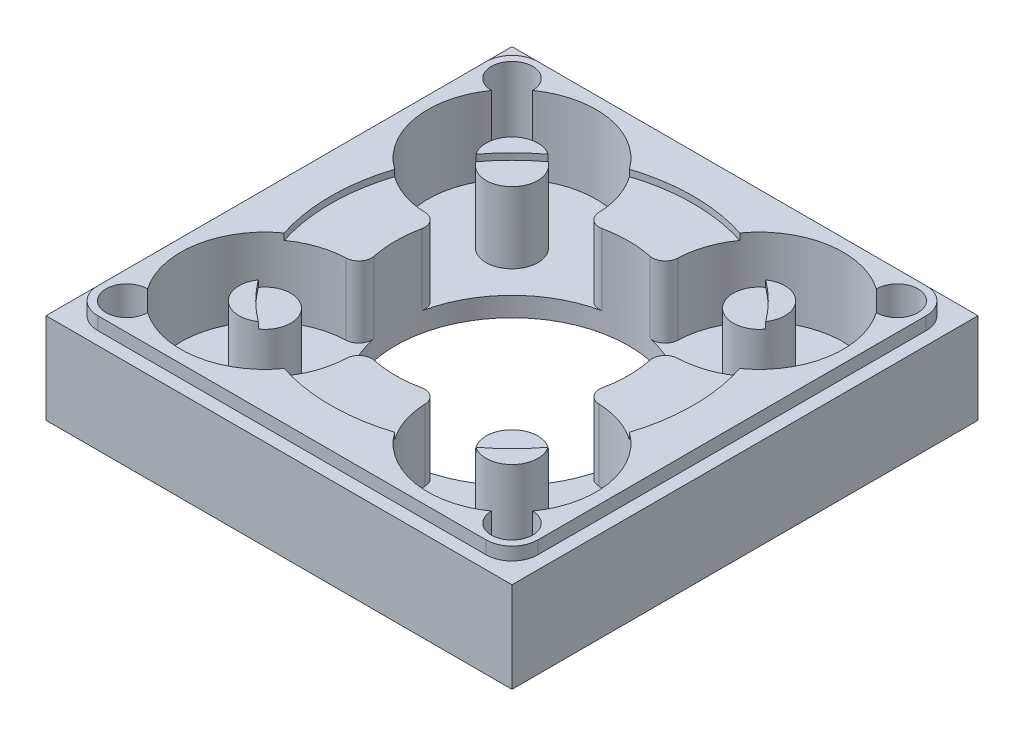
SolidWorks part; units mm, degrees
material "6061 Alloy"
ref_plane "Front Plane" through (0, 0, 0) normal (0, 0, 1) x (1, 0, 0)
ref_plane "Top Plane" through (0, 0, 0) normal (0, 1, 0) x (1, 0, 0)
ref_plane "Right Plane" through (0, 0, 0) normal (1, 0, 0) x (0, 0, -1)
sketch "Sketch1" plane through (0, 0, 0) normal (0, 1, 0) x (1, 0, 0)
  line L1 (-28.575, -28.575) -> (28.575, -28.575)
  line L2 (-28.575, -28.575) -> (-28.575, 28.575)
  line L3 (-28.575, 28.575) -> (28.575, 28.575)
  line L4 (28.575, -28.575) -> (28.575, 28.575)
  line L5 (-28.575, -28.575) -> (28.575, 28.575) construction
  line L6 (-28.575, 28.575) -> (28.575, -28.575) construction
  circle A0 centre (0, 0) radius 14.2875
  point P0 (0, 0)
  dimension "D2" = 28.575
  dimension "D1" = 57.15
extrude "Boss-Extrude1" add sketch "Sketch1" along normal blind 12.7
sketch "Sketch2" plane through (0, 12.7, 0) normal (0, 1, 0) x (1, 0, 0)
  line L1 (-23.8125, -26.9875) -> (23.8125, -26.9875)
  line L2 (-26.9875, -23.8125) -> (-26.9875, 23.8125)
  line L3 (-23.8125, 26.9875) -> (23.8125, 26.9875)
  line L4 (26.9875, -23.8125) -> (26.9875, 23.8125)
  line L5 (-26.9875, -26.9875) -> (26.9875, 26.9875) construction
  line L6 (-26.9875, 26.9875) -> (26.9875, -26.9875) construction
  line L7 (28.575, 28.575) -> (-28.575, 28.575)
  line L8 (28.575, 28.575) -> (28.575, -28.575)
  line L9 (28.575, -28.575) -> (-28.575, -28.575)
  line L10 (-28.575, 28.575) -> (-28.575, -28.575)
  line L11 (28.575, 28.575) -> (-28.575, -28.575) construction
  line L12 (28.575, -28.575) -> (-28.575, 28.575) construction
  arc A0 (23.8125, 26.9875) -> (26.9875, 23.8125) centre (23.8125, 23.8125) cw
  arc A1 (23.8125, -26.9875) -> (26.9875, -23.8125) centre (23.8125, -23.8125) ccw
  arc A2 (-23.8125, -26.9875) -> (-26.9875, -23.8125) centre (-23.8125, -23.8125) cw
  arc A3 (-26.9875, 23.8125) -> (-23.8125, 26.9875) centre (-23.8125, 23.8125) cw
  point P0 (0, 0)
  point P18 (0, 0)
  dimension "D2" = 3.175
  dimension "D1" = 53.975
extrude "Cut-Extrude1" cut sketch "Sketch2" against normal blind 1.5875
sketch "Sketch4" plane through (0, 12.7, 0) normal (0, 1, 0) x (1, 0, 0)
  line L0 (0, 0) -> (15.1542, 15.1542) construction
  line L1 (28.575, -28.575) -> (28.575, 28.575) construction
  circle A0 centre (15.1542, 15.1542) radius 10.3187
  circle A1 centre (15.1542, -15.1542) radius 10.3187
  circle A2 centre (-15.1542, -15.1542) radius 10.3188
  circle A3 centre (-15.1542, 15.1542) radius 10.3188
  circle A4 centre (15.1542, 15.1542) radius 3.175
  circle A5 centre (15.1542, -15.1542) radius 3.175
  circle A6 centre (-15.1542, -15.1542) radius 3.175
  circle A7 centre (-15.1542, 15.1542) radius 3.175
  point P15 (0, 0)
  point P23 (0, 0)
  dimension "D3" = 20.6375
  dimension "D5" = 6.35
  dimension "D1" = 21.4312
  dimension "D2" = 45
  dimension "D4" = 4
  dimension "D6" = 4
extrude "Cut-Extrude3" cut sketch "Sketch4" against normal blind 9.525
sketch "Sketch5" plane through (0, 12.7, 0) normal (0, 1, 0) x (1, 0, 0)
  circle A0 centre (0, 0) radius 22.225
  dimension "D1" = 44.45
extrude "Cut-Extrude4" cut sketch "Sketch5" against normal blind 0.7937
sketch "Sketch6" plane through (0, 0, 0) normal (0, -1, 0) x (1, 0, 0)
  line L1 (23.622, -23.622) -> (-23.622, -23.622) construction
  line L2 (23.622, -23.622) -> (23.622, 23.622) construction
  line L3 (23.622, 23.622) -> (-23.622, 23.622) construction
  line L4 (-23.622, -23.622) -> (-23.622, 23.622) construction
  line L5 (23.622, -23.622) -> (-23.622, 23.622) construction
  line L6 (23.622, 23.622) -> (-23.622, -23.622) construction
  circle A0 centre (-23.622, 23.622) radius 2.54
  circle A1 centre (23.622, 23.622) radius 2.54
  circle A2 centre (23.622, -23.622) radius 2.54
  circle A3 centre (-23.622, -23.622) radius 2.54
  point P0 (0, 0)
  dimension "D2" = 5.08
  dimension "D1" = 47.244
extrude "Cut-Extrude5" cut sketch "Sketch6" against normal through all
sketch "Sketch8" plane through (0, 0, 0) normal (0, -1, 0) x (1, 0, 0)
  circle A0 centre (0, 0) radius 22.225
  dimension "D1" = 44.45
extrude "Cut-Extrude6" cut sketch "Sketch8" against normal blind 0.7937
fillet "Fillet1" radius 1.5875 8 edges at (4.9876, 7.5406, -13.3887) (-4.9876, 7.5406, -13.3887) (-13.3887, 7.5406, -4.9876) (-13.3887, 7.5406, 4.9876) (-4.9876, 7.5406, 13.3887) (4.9876, 7.5406, 13.3887) (13.3887, 7.5406, 4.9876) (13.3887, 7.5406, -4.9876)
